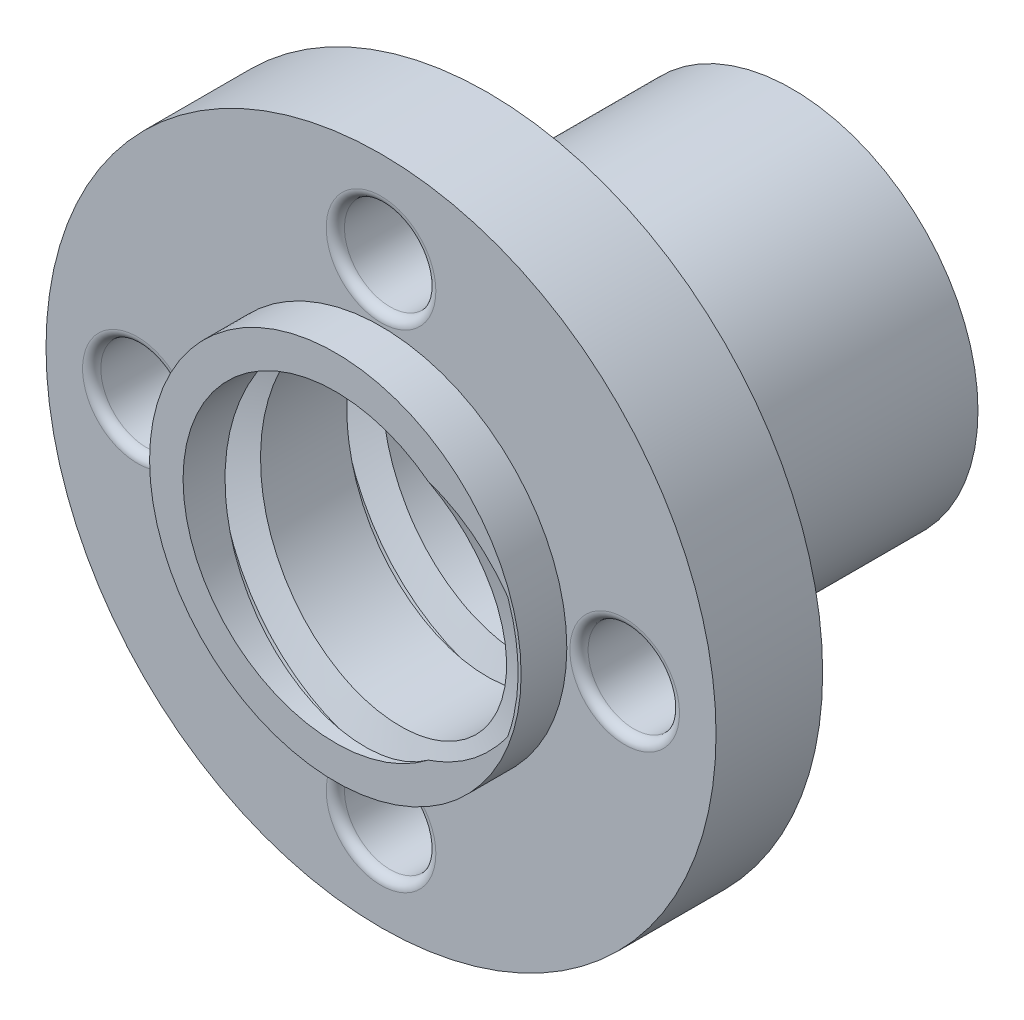
SolidWorks part; units mm, degrees
material "Brass"
ref_plane "Front Plane" through (0, 0, 0) normal (0, 0, 1) x (1, 0, 0)
ref_plane "Top Plane" through (0, 0, 0) normal (0, 1, 0) x (1, 0, 0)
ref_plane "Right Plane" through (0, 0, 0) normal (1, 0, 0) x (0, 0, -1)
sketch "Sketch1" plane through (0, 0, 0) normal (0, 0, 1) x (1, 0, 0)
  circle A0 centre (0, 0) radius 11
  circle A1 centre (0, 0) radius 5.1
  circle A2 centre (0, 0) radius 8 construction
  circle A3 centre (0, 8) radius 1.5
  circle A4 centre (8, 0) radius 1.5
  circle A5 centre (0, -8) radius 1.5
  circle A6 centre (-8, 0) radius 1.5
  point P16 (0, 0)
  dimension "D1" = 22
  dimension "D2" = 10.2
  dimension "D3" = 16
  dimension "D4" = 3
  dimension "D5" = 4
extrude "Boss-Extrude1" add sketch "Sketch1" against normal blind 3.5
sketch "Sketch2" plane through (0, 0, 0) normal (0, 0, 1) x (1, 0, 0)
  circle A0 centre (0, 0) radius 6.1
  circle A1 centre (0, 0) radius 5
  dimension "D1" = 10
  dimension "D2" = 12.2
extrude "Boss-Extrude2" add sketch "Sketch2" along normal blind 1.5 and the other way blind 13.5
sketch "Sketch3" plane through (0, 0, 1.5) normal (0, 0, 1) x (1, 0, 0)
  circle A0 centre (0, 0) radius 5
  dimension "D1" = 10
curve "Helix/Spiral1" pitch 4 height 15 radius 5 centre (0, 0, 1.5) axis (0, 0, -1) start towards (1, 0, 0)
sketch "Sketch4" plane through (0, 0, 0) normal (0, 1, 0) x (1, 0, 0)
  line L0 (4, -0.55) -> (4, -2.45)
  line L1 (4, -2.45) -> (6, -1.7146)
  line L2 (6, -1.7146) -> (6, -1.2854)
  line L3 (6, -1.2854) -> (4, -0.55)
  line L4 (4, -1.5) -> (6, -1.5)
  point P6 (5, -1.5)
  dimension "D1" = 1.9
  dimension "D2" = 2
  dimension "D3" = 69.811
sweep "Cut-Sweep1" cut profiles "Sketch4" path "Helix/Spiral1" align with end faces yes
fillet "Fillet2" radius 0.3 4 edges at (9.5, 0, 0) (1.5, -8, 0) (-6.5, 0, 0) (1.5, 8, 0)
ref_axis "Axis1" through (0, 0, -19.9164) along (0, 0, 1)
